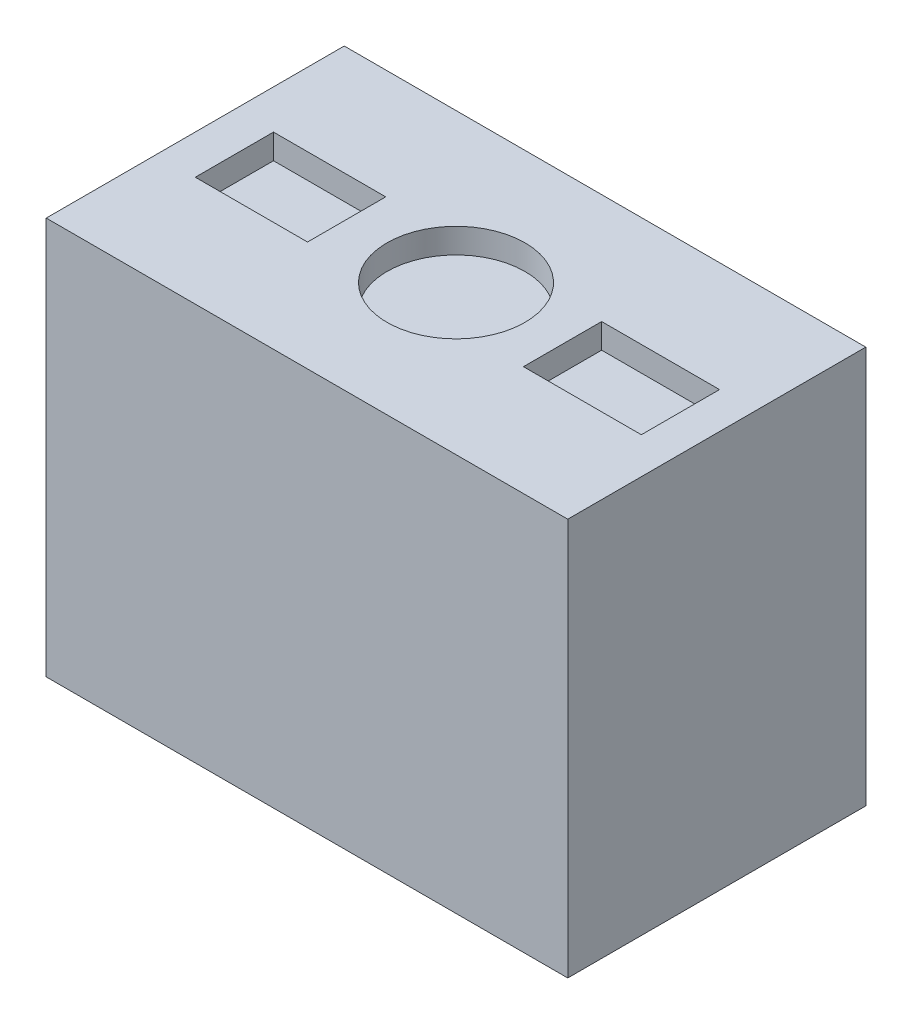
SolidWorks part; units mm, degrees
material "Custom Plastic"
ref_plane "Front Plane" through (0, 0, 0) normal (0, 0, 1) x (1, 0, 0)
ref_plane "Top Plane" through (0, 0, 0) normal (0, 1, 0) x (1, 0, 0)
ref_plane "Right Plane" through (0, 0, 0) normal (1, 0, 0) x (0, 0, -1)
sketch "Sketch1" plane through (0, 0, 0) normal (0, 0, 1) x (1, 0, 0)
  line L1 (-10.5, -8) -> (10.5, -8)
  line L2 (-10.5, -8) -> (-10.5, 8)
  line L3 (-10.5, 8) -> (10.5, 8)
  line L4 (10.5, -8) -> (10.5, 8)
  line L5 (-10.5, -8) -> (10.5, 8) construction
  line L6 (-10.5, 8) -> (10.5, -8) construction
  point P0 (0, 0)
extrude "Boss-Extrude1" add sketch "Sketch1" along normal blind 12
sketch "Sketch2" plane through (0, 0, 0) normal (0, 1, 0) x (1, 0, 0)
  line L1 (4.2901, -7.5746) -> (9.0366, -7.5746)
  line L2 (4.2901, -7.5746) -> (4.2901, -4.4254)
  line L3 (4.2901, -4.4254) -> (9.0366, -4.4254)
  line L4 (9.0366, -7.5746) -> (9.0366, -4.4254)
  line L5 (4.2901, -7.5746) -> (9.0366, -4.4254) construction
  line L6 (4.2901, -4.4254) -> (9.0366, -7.5746) construction
  line L7 (-8.9225, -7.5746) -> (-4.4042, -7.5746)
  line L8 (-8.9225, -7.5746) -> (-8.9225, -4.4254)
  line L9 (-8.9225, -4.4254) -> (-4.4042, -4.4254)
  line L10 (-4.4042, -7.5746) -> (-4.4042, -4.4254)
  line L11 (-8.9225, -7.5746) -> (-4.4042, -4.4254) construction
  line L12 (-8.9225, -4.4254) -> (-4.4042, -7.5746) construction
  circle A0 centre (0, -6) radius 2.7774
  point P2 (6.6634, -6)
  point P7 (-6.6634, -6)
extrude "Cut-Extrude1" cut sketch "Sketch2" against normal blind 1 from surface starting at face at (0, 8, 6)
